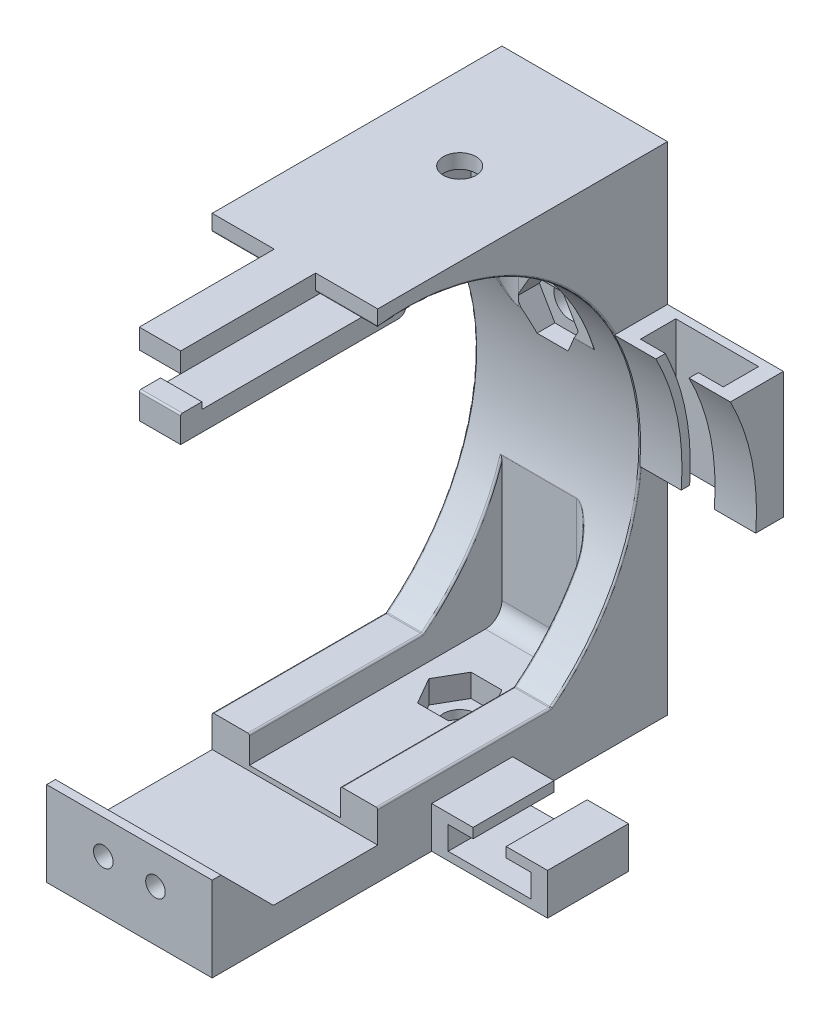
SolidWorks part; units mm, degrees
ref_plane "Front" through (0, 0, 0) normal (0, 0, 1) x (1, 0, 0)
ref_plane "Top" through (0, 0, 0) normal (0, 1, 0) x (1, 0, 0)
ref_plane "Right" through (0, 0, 0) normal (1, 0, 0) x (0, 0, -1)
sketch "Sketch1" plane through (0, 0, 0) normal (0, 0, 1) x (1, 0, 0)
  line L1 (-12.7, 38.1) -> (12.7, 38.1)
  line L2 (-12.7, 38.1) -> (-12.7, -38.1)
  line L3 (-12.7, -38.1) -> (12.7, -38.1)
  line L4 (12.7, 38.1) -> (12.7, -38.1)
  line L5 (-12.7, 38.1) -> (12.7, -38.1) construction
  line L6 (-12.7, -38.1) -> (12.7, 38.1) construction
  point P0 (0, 0)
  dimension "D1" = 25.4
  dimension "D2" = 76.2
extrude "Boss-Extrude1" add sketch "Sketch1" along normal blind 44.45
shell "Shell1" thickness 5.715
sketch "Sketch2" plane through (12.7, 0, 0) normal (1, 0, 0) x (0, 0, -1)
  line L0 (-36.4137, 38.1) -> (-36.4137, -38.1) construction
  line L1 (-44.45, 38.1) -> (0, 38.1) construction
  line L2 (-44.45, -38.1) -> (0, -38.1) construction
  line L3 (-44.45, -28.2144) -> (-17.8665, -28.2144)
  line L4 (-44.45, -28.2144) -> (-44.45, -35.56)
  line L7 (0, -38.1) -> (0, 38.1)
  line L8 (0, 38.1) -> (-44.45, 38.1)
  line L9 (-44.45, 38.1) -> (-44.45, -38.1)
  line L10 (-44.45, -38.1) -> (0, -38.1)
  line L11 (0, -38.1) -> (0, 38.1)
  line L12 (0, 38.1) -> (-44.45, 38.1)
  line L13 (-44.45, 38.1) -> (-44.45, -38.1)
  line L14 (-44.45, -38.1) -> (0, -38.1)
  arc A0 (-44.45, 35.56) -> (-44.45, -35.56) centre (-39.9694, 0) cw
  dimension "D2" = 2.54
  dimension "D3" = 2.54
  dimension "D1" = 0
extrude "Cut-Extrude3" cut sketch "Sketch2" against normal through all both contours A0 L0 L3 | L0 A0 L13 L3
sketch "Sketch4" plane through (0, 38.1, 0) normal (0, 1, 0) x (1, 0, 0)
  line L0 (0, -24.4475) -> (0, 24.4475) construction
  line L1 (-13.97, 0) -> (13.97, 0) construction
  circle A0 centre (0, -19.177) radius 2.5
  dimension "D1" = 5
  dimension "D2" = 19.177
extrude "Cut-Extrude4" cut sketch "Sketch4" against normal through all both
sketch "Sketch5" plane through (0, 0, 5.715) normal (0, 0, 1) x (1, 0, 0)
  line L0 (0, -24.4475) -> (0, 24.4475) construction
  line L1 (12.7, 38.1) -> (-12.7, 38.1) construction
  circle A0 centre (0, 11.684) radius 2.5
  dimension "D1" = 5
  dimension "D2" = 26.416
extrude "Cut-Extrude5" cut sketch "Sketch5" against normal through all both
fillet "Fillet1" radius 2.54 2 edges at (0, 32.385, 5.715) (0, -32.385, 5.715)
fillet "Fillet2" radius 0.254 20 edges at (0, 35.56, 44.45) (-12.7, 13.7899, 6.8872) (12.7, 13.7899, 6.8872) (6.985, -22.9641, 12.4514) (5.0613, -10.7899, 5.7909) (6.985, 23.4535, 12.8673) (0, 32.385, 24.6136) (-6.985, 25.8681, 15.1615) (-5.0613, 10.7899, 5.7909) (-3.3356, 10.5464, 5.715) (4.6056, 10.5464, 5.715) (-1.27, -10.5464, 5.715) (-0.2184, 9.1936, 5.3274) (6.985, -28.2144, 31.1583) (-6.985, -28.2144, 31.1583) (-12.7, -28.2144, 31.1583) (12.7, -28.2144, 31.1583) (-6.985, -20.3105, 10.4385) (-9.8425, -28.2144, 17.8665) (9.8425, -28.2144, 17.8665)
sketch "Sketch6" plane through (0, 32.385, 0) normal (0, -1, 0) x (1, 0, 0)
  circle A0 centre (0, 19.177) radius 2.5 construction
  circle A1 centre (0, 19.177) radius 2.5
sketch "Sketch7" plane through (0, -32.385, 0) normal (0, 1, 0) x (1, 0, 0)
  line L1 (-2.3671, -23.277) -> (2.3671, -23.277)
  line L2 (2.3671, -23.277) -> (4.7343, -19.177)
  line L3 (4.7343, -19.177) -> (2.3671, -15.077)
  line L4 (2.3671, -15.077) -> (-2.3671, -15.077)
  line L5 (-2.3671, -15.077) -> (-4.7343, -19.177)
  line L6 (-4.7343, -19.177) -> (-2.3671, -23.277)
  circle A0 centre (0, -19.177) radius 2.5 construction
  circle A1 centre (0, -19.177) radius 2.5
  circle A2 centre (0, -19.177) radius 4.1 construction
  dimension "D1" = 8.2
extrude "Cut-Extrude6" cut sketch "Sketch7" against normal blind 3.5
sketch "Sketch8" plane through (0, 0, 5.715) normal (0, 0, 1) x (1, 0, 0)
  line L1 (4.7343, 11.684) -> (2.3671, 15.784)
  line L2 (2.3671, 15.784) -> (-2.3671, 15.784)
  line L3 (-2.3671, 15.784) -> (-4.7343, 11.684)
  line L4 (-4.7343, 11.684) -> (-2.3671, 7.584)
  line L5 (-2.3671, 7.584) -> (2.3671, 7.584)
  line L6 (2.3671, 7.584) -> (4.7343, 11.684)
  circle A0 centre (0, 11.684) radius 2.5 construction
  circle A1 centre (0, 11.684) radius 2.5
  circle A2 centre (0, 11.684) radius 4.1 construction
  dimension "D1" = 8.2
extrude "Cut-Extrude7" cut sketch "Sketch8" against normal blind 3.5
sketch "Sketch9" plane through (0, 32.385, 0) normal (0, -1, 0) x (1, 0, 0)
  line L1 (2.3671, 15.077) -> (4.7343, 19.177)
  line L2 (4.7343, 19.177) -> (2.3671, 23.277)
  line L3 (2.3671, 23.277) -> (-2.3671, 23.277)
  line L4 (-2.3671, 23.277) -> (-4.7343, 19.177)
  line L5 (-4.7343, 19.177) -> (-2.3671, 15.077)
  line L6 (-2.3671, 15.077) -> (2.3671, 15.077)
  circle A0 centre (0, 19.177) radius 2.5 construction
  circle A1 centre (0, 19.177) radius 2.5
  circle A2 centre (0, 19.177) radius 4.1 construction
  dimension "D1" = 8.2
extrude "Cut-Extrude8" cut sketch "Sketch9" against normal blind 3.5
sketch "Sketch10" plane through (0, 0, 0) normal (1, 0, 0) x (0, 0, -1)
  line L1 (-30.5295, 38.1) -> (-65.1574, 38.1)
  line L2 (-30.5295, 38.1) -> (-30.5295, 35.052)
  line L3 (-30.5295, 35.052) -> (-65.1574, 35.052)
  line L4 (-65.1574, 38.1) -> (-65.1574, 35.052)
  line L5 (-44.45, -28.4684) -> (-44.45, -38.1)
  line L6 (-44.45, -28.4684) -> (-44.45, -38.1)
  line L8 (0, 38.1) -> (-44.45, 38.1)
  line L9 (-44.45, 38.1) -> (-44.45, 35.8469)
  line L13 (0, 38.1) -> (-44.45, 38.1)
  line L14 (-44.45, 38.1) -> (-44.45, 35.8469)
  line L15 (-30.5295, 35.052) -> (-33.0695, 35.052)
  line L16 (-30.5295, 35.052) -> (-30.5295, 28.702)
  line L17 (-30.5295, 28.702) -> (-33.0695, 28.702)
  line L18 (-33.0695, 35.052) -> (-33.0695, 28.702)
  line L19 (-30.5295, 28.702) -> (-65.1574, 28.702)
  line L20 (-30.5295, 28.702) -> (-30.5295, 26.924)
  line L21 (-31.7995, 25.654) -> (-65.1574, 25.654)
  line L22 (-65.1574, 28.702) -> (-65.1574, 25.654)
  line L23 (-65.1574, 28.702) -> (-61.9009, 28.702)
  line L24 (-65.1574, 28.702) -> (-65.1574, 29.464)
  line L25 (-64.9034, 29.718) -> (-61.9009, 29.718)
  line L26 (-61.9009, 28.702) -> (-61.9009, 29.718)
  line L31 (-44.45, -38.1) -> (0, -38.1)
  line L32 (-44.45, -38.1) -> (0, -38.1)
  line L33 (0, -38.1) -> (0, 38.1)
  line L34 (0, -38.1) -> (0, 38.1)
  line L35 (-17.9543, -28.4684) -> (-44.45, -28.4684)
  line L36 (-17.9543, -28.4684) -> (-44.45, -28.4684)
  arc A0 (-64.9034, 29.718) -> (-65.1574, 29.464) centre (-64.9034, 29.464) ccw
  arc A1 (-30.5295, 26.924) -> (-31.7995, 25.654) centre (-31.7995, 26.924) cw
  arc A3 (-17.6401, -28.3595) -> (-44.4481, 35.8162) centre (-39.9694, 0) ccw
  arc A4 (-44.45, 35.8469) -> (-44.4481, 35.8162) centre (-44.196, 35.8469) ccw
  arc A5 (-17.9543, -28.4684) -> (-17.6401, -28.3595) centre (-17.9543, -27.9604) ccw
  arc A6 (-17.6401, -28.3595) -> (-44.4481, 35.8162) centre (-39.9694, 0) ccw
  arc A7 (-44.45, 35.8469) -> (-44.4481, 35.8162) centre (-44.196, 35.8469) ccw
  arc A11 (-17.9543, -28.4684) -> (-17.6401, -28.3595) centre (-17.9543, -27.9604) ccw
  point P26 (-65.1574, 29.718)
  dimension "D6" = 0.254
  dimension "D8" = 1.27
  dimension "D2" = 3.048
  dimension "D3" = 3.048
  dimension "D4" = 1.016
  dimension "D5" = 6.35
  dimension "D7" = 2.54
  dimension "D1" = 0
extrude "Boss-Extrude2" add sketch "Sketch10" along normal mid plane 6.35 contours L2 L1 L4 L3 | L16 L15 L18 L17 | L20 A1 L21 L22 L19 | L24 A0 L25 L26 L23
sketch "Sketch11" plane through (0, 0, 44.45) normal (0, 0, 1) x (1, 0, 0)
  line L1 (-12.7, -38.1) -> (12.7, -38.1)
  line L2 (-12.7, -38.1) -> (-12.7, -33.147)
  line L3 (-12.7, -33.147) -> (12.7, -33.147)
  line L4 (12.7, -38.1) -> (12.7, -33.147)
  line L8 (12.446, -28.2144) -> (7.239, -28.2144)
  line L9 (6.985, -28.4684) -> (6.985, -32.385)
  line L10 (6.985, -32.385) -> (-6.985, -32.385)
  line L11 (-6.985, -32.385) -> (-6.985, -28.4684)
  line L12 (-7.239, -28.2144) -> (-12.446, -28.2144)
  line L13 (-12.7, -28.4684) -> (-12.7, -38.1)
  line L14 (-12.7, -38.1) -> (12.7, -38.1)
  line L15 (12.7, -38.1) -> (12.7, -28.4684)
  line L16 (12.446, -28.2144) -> (7.239, -28.2144)
  line L17 (6.985, -28.4684) -> (6.985, -32.385)
  line L18 (6.985, -32.385) -> (-6.985, -32.385)
  line L19 (-6.985, -32.385) -> (-6.985, -28.4684)
  line L20 (-7.239, -28.2144) -> (-12.446, -28.2144)
  line L21 (-12.7, -28.4684) -> (-12.7, -38.1)
  line L22 (-12.7, -38.1) -> (12.7, -38.1)
  line L23 (12.7, -38.1) -> (12.7, -28.4684)
  arc A4 (7.239, -28.2144) -> (6.985, -28.4684) centre (7.239, -28.4684) ccw
  arc A5 (-6.985, -28.4684) -> (-7.239, -28.2144) centre (-7.239, -28.4684) ccw
  arc A6 (-12.446, -28.2144) -> (-12.7, -28.4684) centre (-12.446, -28.4684) ccw
  arc A7 (12.7, -28.4684) -> (12.446, -28.2144) centre (12.446, -28.4684) ccw
  arc A8 (7.239, -28.2144) -> (6.985, -28.4684) centre (7.239, -28.4684) ccw
  arc A9 (-6.985, -28.4684) -> (-7.239, -28.2144) centre (-7.239, -28.4684) ccw
  arc A10 (-12.446, -28.2144) -> (-12.7, -28.4684) centre (-12.446, -28.4684) ccw
  arc A11 (12.7, -28.4684) -> (12.446, -28.2144) centre (12.446, -28.4684) ccw
  line M25 (-12.7, -28.4684) -> (-12.7, -38.1)
  line M26 (-12.7, -38.1) -> (12.7, -38.1)
  line M27 (12.7, -38.1) -> (12.7, -28.4684)
  dimension "D2" = 0.762
  dimension "D1" = 0
extrude "Boss-Extrude3" add sketch "Sketch11" along normal blind 25.4 contours L3 M25 M26 M27
sketch "Sketch13" plane through (0, 0, 69.85) normal (0, 0, 1) x (1, 0, 0)
  line L0 (12.7, -28.3595) -> (12.7, 36.0952) construction
  line L1 (-12.7, -38.1) -> (12.7, -38.1)
  line L2 (-12.7, -38.1) -> (-12.7, -25.1)
  line L3 (-12.7, -25.1) -> (12.7, -25.1)
  line L4 (12.7, -38.1) -> (12.7, -25.1)
  dimension "D1" = 13
extrude "Boss-Extrude6" add sketch "Sketch13" against normal blind 1.27
chamfer "Chamfer1" distance 8.128 angle 45 1 edges at (0, -33.147, 68.58)
sketch "Sketch14" plane through (0, 0, 69.85) normal (0, 0, 1) x (1, 0, 0)
  line L0 (-4, -30.297) -> (4, -30.297) construction
  line L1 (0, -38.4175) -> (0, 38.4175) construction
  circle A0 centre (-4, -30.297) radius 1.5
  circle A1 centre (4, -30.297) radius 1.5
  point P4 (0, -30.297)
  dimension "D2" = 3
  dimension "D1" = 8
extrude "Cut-Extrude9" cut sketch "Sketch14" against normal up to next
sketch "Sketch15" plane through (0, 0, 69.85) normal (0, 0, 1) x (1, 0, 0)
  line L1 (-2.369, -27.472) -> (-5.631, -27.472)
  line L2 (-5.631, -27.472) -> (-7.262, -30.297)
  line L3 (-7.262, -30.297) -> (-5.631, -33.122)
  line L4 (12.7, -38.1) -> (12.7, -25.1)
  line L5 (12.7, -25.1) -> (-12.7, -25.1)
  line L6 (-12.7, -25.1) -> (-12.7, -38.1)
  line L7 (-12.7, -38.1) -> (12.7, -38.1)
  line L8 (12.7, -38.1) -> (12.7, -25.1)
  line L9 (12.7, -25.1) -> (-12.7, -25.1)
  line L10 (-12.7, -25.1) -> (-12.7, -38.1)
  line L11 (-12.7, -38.1) -> (12.7, -38.1)
  line L12 (-5.631, -33.122) -> (-2.369, -33.122)
  line L13 (-2.369, -33.122) -> (-0.738, -30.297)
  line L14 (-0.738, -30.297) -> (-2.369, -27.472)
  line L15 (5.631, -27.472) -> (2.369, -27.472)
  line L16 (2.369, -27.472) -> (0.738, -30.297)
  line L17 (0.738, -30.297) -> (2.369, -33.122)
  line L18 (2.369, -33.122) -> (5.631, -33.122)
  line L19 (5.631, -33.122) -> (7.262, -30.297)
  line L20 (7.262, -30.297) -> (5.631, -27.472)
  circle A0 centre (4, -30.297) radius 1.5 construction
  circle A1 centre (-4, -30.297) radius 1.5 construction
  circle A2 centre (4, -30.297) radius 1.5
  circle A3 centre (-4, -30.297) radius 1.5
  circle A4 centre (-4, -30.297) radius 2.825 construction
  circle A5 centre (4, -30.297) radius 2.825 construction
  dimension "D2" = 5.65
  dimension "D1" = 0
extrude "Cut-Extrude10" cut sketch "Sketch15" against normal blind 12.7 from offset 2.54 contours L1 L2 L3 L12 L13 L14 | L15 L16 L17 L18 L19 L20 offset against normal yes
sketch "Sketch16" plane through (0, 0, 0) normal (0, 0, 1) x (1, 0, 0)
  line L0 (12.7, -28.3595) -> (12.7, 36.0952) construction
  line L1 (12.7, 16.4632) -> (30.48, 16.4632)
  line L2 (12.7, 16.4632) -> (12.7, -2.9134)
  line L3 (12.7, -2.9134) -> (30.48, -2.9134)
  line L4 (30.48, 16.4632) -> (30.48, -2.9134)
  line L6 (30.48, 16.4632) -> (22.86, 16.4632)
  line L7 (30.48, 16.4632) -> (30.48, -2.9134)
  line L8 (30.48, -2.9134) -> (22.86, -2.9134)
  line L10 (12.7, 16.4632) -> (15.24, 16.4632)
  line L11 (12.7, 16.4632) -> (12.7, -2.9134)
  line L12 (12.7, -2.9134) -> (15.24, -2.9134)
  dimension "D1" = 17.78
extrude "Boss-Extrude7" add sketch "Sketch16" along normal blind 1.27 contours L2 L1 L4 L3
sketch "Sketch17" plane through (0, 0, 1.27) normal (0, 0, 1) x (1, 0, 0)
  line L0 (12.7, -2.9134) -> (30.48, -2.9134) construction
  line L1 (30.48, 16.4632) -> (27.94, 16.4632)
  line L2 (30.48, 16.4632) -> (30.48, -2.9134)
  line L3 (30.48, -2.9134) -> (27.94, -2.9134)
  line L4 (27.94, 16.4632) -> (27.94, -2.9134)
  line L6 (12.7, 16.4632) -> (15.24, 16.4632)
  line L7 (12.7, 16.4632) -> (12.7, -2.9134)
  line L8 (12.7, -2.9134) -> (15.24, -2.9134)
  line L9 (15.24, 16.4632) -> (15.24, -2.9134)
  dimension "D1" = 2.54
  dimension "D2" = 2.54
extrude "Boss-Extrude8" add sketch "Sketch17" along normal up to surface (6.8631 mm away)
sketch "Sketch18" plane through (15.24, 0, 0) normal (1, 0, 0) x (0, 0, -1)
  line L3 (-4.2468, -2.9134) -> (-1.27, -2.9134)
  line L4 (-1.27, -2.9134) -> (-1.27, 16.4632)
  line L5 (-1.27, 16.4632) -> (-8.1331, 16.4632)
  line L6 (-4.2468, -2.9134) -> (-1.27, -2.9134)
  line L7 (-1.27, -2.9134) -> (-1.27, 16.4632)
  line L8 (-1.27, 16.4632) -> (-8.1331, 16.4632)
  line L9 (-2.54, 15.1932) -> (-6.1108, 15.1932) construction
  line L10 (-2.54, -1.6434) -> (-2.54, 15.1932) construction
  line L11 (-2.8946, -1.6434) -> (-2.54, -1.6434) construction
  line L12 (-6.1108, 15.1932) -> (-6.6807, 16.4632)
  line L13 (-2.8946, -1.6434) -> (-2.9509, -2.9134)
  arc A0 (-2.8946, -1.6434) -> (-6.1108, 15.1932) centre (-39.9694, 0) ccw
  arc A1 (-4.2468, -2.9134) -> (-8.1331, 16.4632) centre (-39.9694, 0) ccw
  arc A2 (-4.2468, -2.9134) -> (-8.1331, 16.4632) centre (-39.9694, 0) ccw
  arc M10 (-8.1331, 16.4632) -> (-4.2468, -2.9134) centre (-39.9694, 0) cw
  line M11 (-4.2468, -2.9134) -> (-1.27, -2.9134)
  dimension "D1" = 0
  dimension "D2" = 1.27
extrude "Boss-Extrude9" add sketch "Sketch18" along normal blind 3.81 contours L13 A0 L12 L8 M10 M11
sketch "Sketch19" plane through (27.94, 0, 0) normal (-1, 0, 0) x (0, 0, 1)
  line L4 (2.8946, -1.6434) -> (2.9509, -2.9134)
  line L5 (6.6807, 16.4632) -> (6.1108, 15.1932)
  line L6 (8.1331, 16.4632) -> (6.6807, 16.4632)
  line L7 (2.9509, -2.9134) -> (4.2468, -2.9134)
  line L8 (2.8946, -1.6434) -> (2.9509, -2.9134)
  line L9 (6.6807, 16.4632) -> (6.1108, 15.1932)
  line L10 (8.1331, 16.4632) -> (6.6807, 16.4632)
  line L11 (2.9509, -2.9134) -> (4.2468, -2.9134)
  arc A2 (6.1108, 15.1932) -> (2.8946, -1.6434) centre (39.9694, 0) ccw
  arc A3 (8.1331, 16.4632) -> (4.2468, -2.9134) centre (39.9694, 0) ccw
  arc A4 (6.1108, 15.1932) -> (2.8946, -1.6434) centre (39.9694, 0) ccw
  arc A5 (8.1331, 16.4632) -> (4.2468, -2.9134) centre (39.9694, 0) ccw
  dimension "D1" = 0
extrude "Boss-Extrude10" add sketch "Sketch19" along normal blind 3.81
sketch "Sketch20" plane through (0, -38.1, 0) normal (0, -1, 0) x (1, 0, 0)
  line L0 (12.7, 60.452) -> (12.7, 44.45) construction
  line L1 (12.7, 36.1802) -> (30.48, 36.1802)
  line L2 (12.7, 36.1802) -> (12.7, 23.7612)
  line L3 (12.7, 23.7612) -> (30.48, 23.7612)
  line L4 (30.48, 36.1802) -> (30.48, 23.7612)
  line L5 (30.48, 4.2468) -> (30.48, 0) construction
  point P6 (28.2899, 36.1802)
extrude "Boss-Extrude11" add sketch "Sketch20" against normal blind 1.27
sketch "Sketch21" plane through (0, -36.83, 0) normal (0, 1, 0) x (1, 0, 0)
  line L0 (12.7, -44.45) -> (12.7, 0) construction
  line L1 (12.7, -23.7612) -> (15.24, -23.7612)
  line L2 (12.7, -23.7612) -> (12.7, -36.1802)
  line L3 (12.7, -36.1802) -> (15.24, -36.1802)
  line L4 (15.24, -23.7612) -> (15.24, -36.1802)
  line L5 (12.7, -23.7612) -> (30.48, -23.7612) construction
  line L6 (30.48, -36.1802) -> (12.7, -36.1802) construction
  line L8 (30.48, -23.7612) -> (27.94, -23.7612)
  line L9 (30.48, -23.7612) -> (30.48, -36.1802)
  line L10 (30.48, -36.1802) -> (27.94, -36.1802)
  line L11 (27.94, -23.7612) -> (27.94, -36.1802)
  dimension "D1" = 2.54
  dimension "D2" = 2.54
extrude "Boss-Extrude12" add sketch "Sketch21" along normal blind 5.08
sketch "Sketch22" plane through (15.24, 0, 0) normal (1, 0, 0) x (0, 0, -1)
  line L0 (-23.7612, -31.75) -> (-23.7612, -36.83) construction
  line L1 (-23.7612, -31.75) -> (-36.1802, -31.75)
  line L2 (-23.7612, -31.75) -> (-23.7612, -33.274)
  line L3 (-23.7612, -33.274) -> (-36.1802, -33.274)
  line L4 (-36.1802, -31.75) -> (-36.1802, -33.274)
  line L5 (-36.1802, -31.75) -> (-23.7612, -31.75) construction
  line L6 (-36.1802, -31.75) -> (-36.1802, -36.83) construction
  dimension "D1" = 1.524
extrude "Boss-Extrude13" add sketch "Sketch22" along normal up to surface (3.81 mm away) up to face at (19.05, 6.8518, 4.7783)
sketch "Sketch23" plane through (27.94, 0, 0) normal (-1, 0, 0) x (0, 0, 1)
  line L4 (23.7612, -31.75) -> (23.7612, -33.274)
  line L5 (36.1802, -31.75) -> (23.7612, -31.75)
  line L6 (36.1802, -33.274) -> (36.1802, -31.75)
  line L7 (23.7612, -33.274) -> (36.1802, -33.274)
  line L8 (23.7612, -31.75) -> (23.7612, -33.274)
  line L9 (36.1802, -31.75) -> (23.7612, -31.75)
  line L10 (36.1802, -33.274) -> (36.1802, -31.75)
  line L11 (23.7612, -33.274) -> (36.1802, -33.274)
  dimension "D1" = 0
extrude "Boss-Extrude14" add sketch "Sketch23" along normal up to surface (3.81 mm away) up to face at (24.13, 6.8518, 4.7783)
